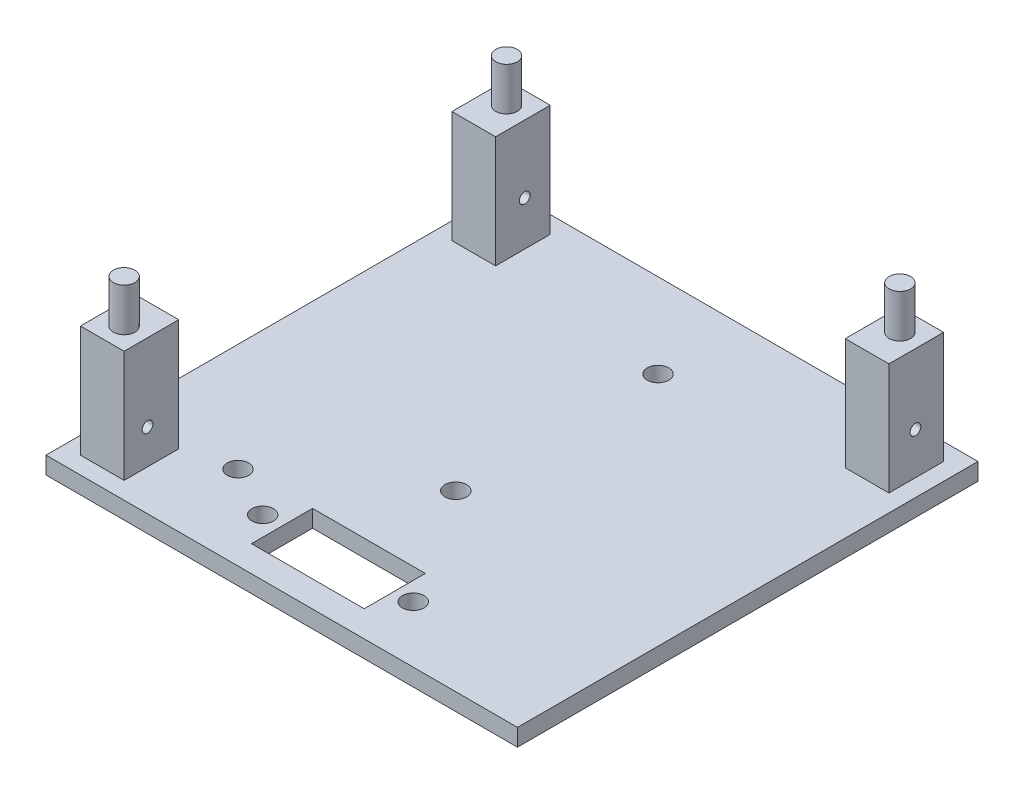
SolidWorks part; units mm, degrees
ref_plane "Front Plane" through (0, 0, 0) normal (0, 0, 1) x (1, 0, 0)
ref_plane "Top Plane" through (0, 0, 0) normal (0, 1, 0) x (1, 0, 0)
ref_plane "Right Plane" through (0, 0, 0) normal (1, 0, 0) x (0, 0, -1)
sketch "Sketch2" plane through (0, 0, 0) normal (0, 1, 0) x (1, 0, 0)
  line L1 (27.4, -26.765) -> (-27.4, -26.765)
  line L2 (27.4, -26.765) -> (27.4, 26.765)
  line L3 (27.4, 26.765) -> (-27.4, 26.765)
  line L4 (-27.4, -26.765) -> (-27.4, 26.765)
  line L5 (27.4, -26.765) -> (-27.4, 26.765) construction
  line L6 (27.4, 26.765) -> (-27.4, -26.765) construction
  point P0 (0, 0)
  dimension "D1" = 54.8
  dimension "D2" = 53.53
extrude "Boss-Extrude1" add sketch "Sketch2" along normal blind 2
sketch "Sketch3" plane through (0, 2, 0) normal (0, 1, 0) x (1, 0, 0)
  line L0 (27.4, 26.765) -> (-27.4, 26.765) construction
  line L1 (-20.32, 18.415) -> (-25.4, 18.415)
  line L2 (-20.32, 18.415) -> (-20.32, 24.765)
  line L3 (-20.32, 24.765) -> (-25.4, 24.765)
  line L4 (-25.4, 18.415) -> (-25.4, 24.765)
  line L5 (-20.32, 18.415) -> (-25.4, 24.765) construction
  line L6 (-20.32, 24.765) -> (-25.4, 18.415) construction
  line L7 (-27.4, 26.765) -> (-27.4, -26.765) construction
  line L8 (27.4, -26.765) -> (27.4, 26.765) construction
  line L9 (25.4, 18.415) -> (20.32, 18.415)
  line L10 (25.4, 18.415) -> (25.4, 24.765)
  line L11 (25.4, 24.765) -> (20.32, 24.765)
  line L12 (20.32, 18.415) -> (20.32, 24.765)
  line L13 (25.4, 18.415) -> (20.32, 24.765) construction
  line L14 (25.4, 24.765) -> (20.32, 18.415) construction
  line L15 (-27.4, -26.765) -> (27.4, -26.765) construction
  line L16 (-20.32, -24.765) -> (-25.4, -24.765)
  line L17 (-20.32, -24.765) -> (-20.32, -18.415)
  line L18 (-20.32, -18.415) -> (-25.4, -18.415)
  line L19 (-25.4, -24.765) -> (-25.4, -18.415)
  line L20 (-20.32, -24.765) -> (-25.4, -18.415) construction
  line L21 (-20.32, -18.415) -> (-25.4, -24.765) construction
  point P0 (-22.86, 21.59)
  point P7 (22.86, 21.59)
  point P16 (-22.86, -21.59)
  dimension "D1" = 2
  dimension "D2" = 2
  dimension "D3" = 5.08
  dimension "D4" = 6.35
  dimension "D5" = 5.08
  dimension "D6" = 6.35
  dimension "D7" = 2
  dimension "D8" = 2
  dimension "D9" = 2
  dimension "D10" = 2
  dimension "D11" = 5.08
  dimension "D12" = 6.35
extrude "Boss-Extrude2" add sketch "Sketch3" along normal blind 13
sketch "Sketch6" plane through (0, 15, 0) normal (0, 1, 0) x (1, 0, 0)
  line L0 (25.4, 24.765) -> (20.32, 24.765) construction
  line L2 (-20.32, 24.765) -> (-25.4, 24.765) construction
  line L3 (-25.4, 24.765) -> (-25.4, 18.415) construction
  line L4 (20.32, 24.765) -> (20.32, 18.415) construction
  line L6 (-20.32, -24.765) -> (-20.32, -18.415) construction
  line L8 (-25.4, -24.765) -> (-20.32, -24.765) construction
  circle A0 centre (-22.86, 22.225) radius 1.25
  circle A1 centre (22.86, 22.225) radius 1.25
  circle A2 centre (-22.86, -22.225) radius 1.25
  point P4 (-22.86, 24.765)
  point P17 (-22.86, -24.765)
  point P19 (22.86, 24.765)
  dimension "D1" = 2.54
  dimension "D3" = 2.54
  dimension "D5" = 2.54
  dimension "D2" = 2.54
  dimension "D4" = 2.54
  dimension "D6" = 2.54
extrude "Boss-Extrude3" add sketch "Sketch6" along normal blind 5
sketch "Sketch7" plane through (0, 0, 0) normal (0, -1, 0) x (-1, 0, 0)
  line L1 (6.55, -23.7306) -> (-6.55, -23.7306)
  line L2 (6.55, -23.7306) -> (6.55, -16.6306)
  line L3 (6.55, -16.6306) -> (-6.55, -16.6306)
  line L4 (-6.55, -23.7306) -> (-6.55, -16.6306)
  line L5 (6.55, -23.7306) -> (-6.55, -16.6306) construction
  line L6 (6.55, -16.6306) -> (-6.55, -23.7306) construction
  point P0 (0, -20.1806)
  dimension "D1" = 13.1
  dimension "D2" = 7.1
extrude "Cut-Extrude1" cut sketch "Sketch7" against normal up to next
sketch "Sketch8" plane through (0, 0, 0) normal (0, -1, 0) x (1, 0, 0)
  circle A0 centre (0, 6.5308) radius 1.25
  circle A1 centre (0, -16.9692) radius 1.25
  dimension "D1" = 23.5
extrude "Cut-Extrude2" cut sketch "Sketch8" against normal up to next
sketch "Sketch9" plane through (-25.4, 0, 0) normal (-1, 0, 0) x (0, 0, 1)
  circle A1 centre (-21.8045, 7.1574) radius 0.625
extrude "Cut-Extrude4" cut sketch "Sketch9" against normal up to next
sketch "Sketch10" plane through (25.4, 0, 0) normal (1, 0, 0) x (0, 0, -1)
  circle A0 centre (21.4936, 6.854) radius 0.625
extrude "Cut-Extrude5" cut sketch "Sketch10" against normal up to next
sketch "Sketch11" plane through (-25.4, 0, 0) normal (-1, 0, 0) x (0, 0, 1)
  circle A0 centre (22.0455, 6.0227) radius 0.625
extrude "Cut-Extrude6" cut sketch "Sketch11" against normal up to next
sketch "Sketch12" plane through (0, 2, 0) normal (0, 1, 0) x (1, 0, 0)
  circle A0 centre (-14.8355, -17.0172) radius 1.25
extrude "Cut-Extrude7" cut sketch "Sketch12" against normal up to next
sketch "Sketch13" plane through (0, 2, 0) normal (0, 1, 0) x (1, 0, 0)
  line L0 (-6.55, -23.7306) -> (-6.55, -16.6306) construction
  circle A0 centre (-8.8, -20.1806) radius 1.25
  circle A1 centre (8.7, -20.1806) radius 1.25
  point P2 (-6.55, -20.1806)
  dimension "D1" = 17.5
  dimension "D2" = 2.25
extrude "Cut-Extrude8" cut sketch "Sketch13" against normal up to next
